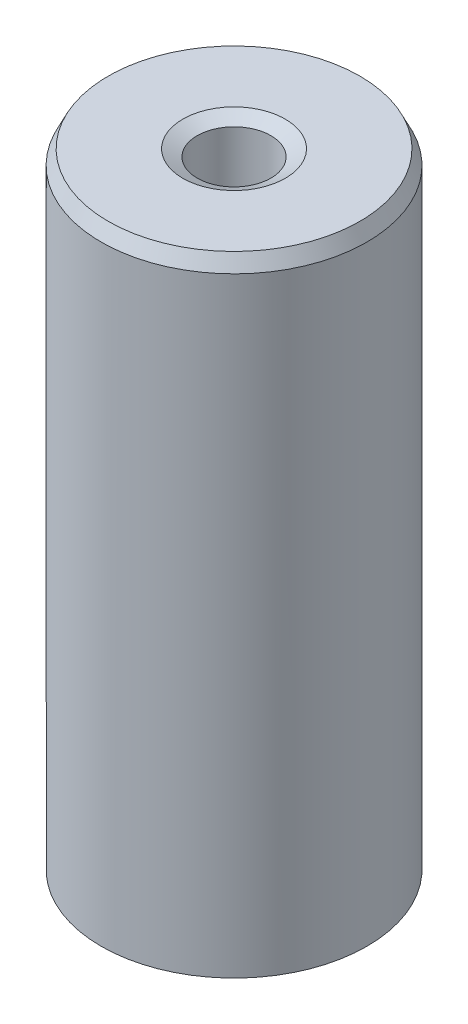
SolidWorks part; units mm, degrees
ref_plane "Front Plane" through (0, 0, 0) normal (0, 0, 1) x (1, 0, 0)
ref_plane "Top Plane" through (0, 0, 0) normal (0, 1, 0) x (1, 0, 0)
ref_plane "Right Plane" through (0, 0, 0) normal (1, 0, 0) x (0, 0, -1)
sketch "Sketch1" plane through (0, 0, 0) normal (0, 1, 0) x (1, 0, 0)
  circle A0 centre (0, 0) radius 5
  dimension "SLEEVE_OD" = 10
extrude "Boss-Extrude1" add sketch "Sketch1" along normal blind 23.753
sketch "Sketch2" plane through (0, 0, 0) normal (0, 1, 0) x (1, 0, 0)
  circle A0 centre (0, 0) radius 1.3864
  dimension "BORE_D" = 2.7729
extrude "Cut-Extrude1" cut sketch "Sketch2" along normal through all
chamfer "Chamfer1" distance 0.5422 angle 26.144 4 edges at (0, 23.753, 1.3864) (0, 0, 1.3864) (0, 0, 5) (0, 23.753, 5) first distance on face at (0, 23.753, 1.3864) first distance on face at (0, 0, 1.3864) first distance on face at (0, 23.753, 5)
